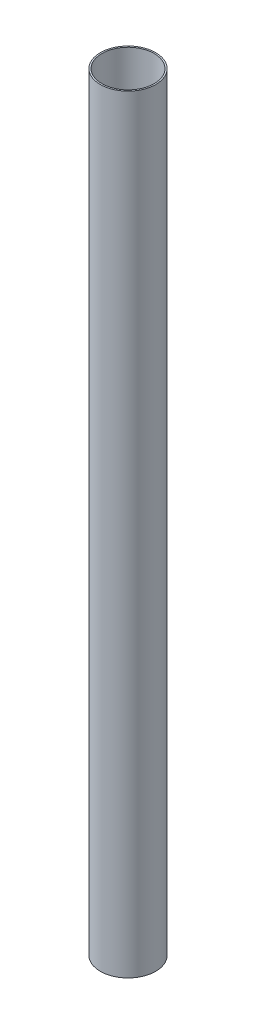
SolidWorks part; units mm, degrees
material "6063-T6"
ref_plane "Front Plane" through (0, 0, 0) normal (0, 0, 1) x (1, 0, 0)
ref_plane "Top Plane" through (0, 0, 0) normal (0, 1, 0) x (1, 0, 0)
ref_plane "Right Plane" through (0, 0, 0) normal (1, 0, 0) x (0, 0, -1)
sketch "Sketch1" plane through (0, 0, 0) normal (0, 0, 1) x (1, 0, 0)
  line L0 (0, 0) -> (0, 45.6531) construction
  line L1 (25.5143, 52.2108) -> (26.9875, 52.2108)
  line L2 (25.5143, 52.2108) -> (25.5143, -697.0892)
  line L3 (25.5143, -697.0892) -> (26.9875, -697.0892)
  line L4 (26.9875, 52.2108) -> (26.9875, -697.0892)
revolve "Revolve1" add sketch "Sketch1" angle 360 about L0
